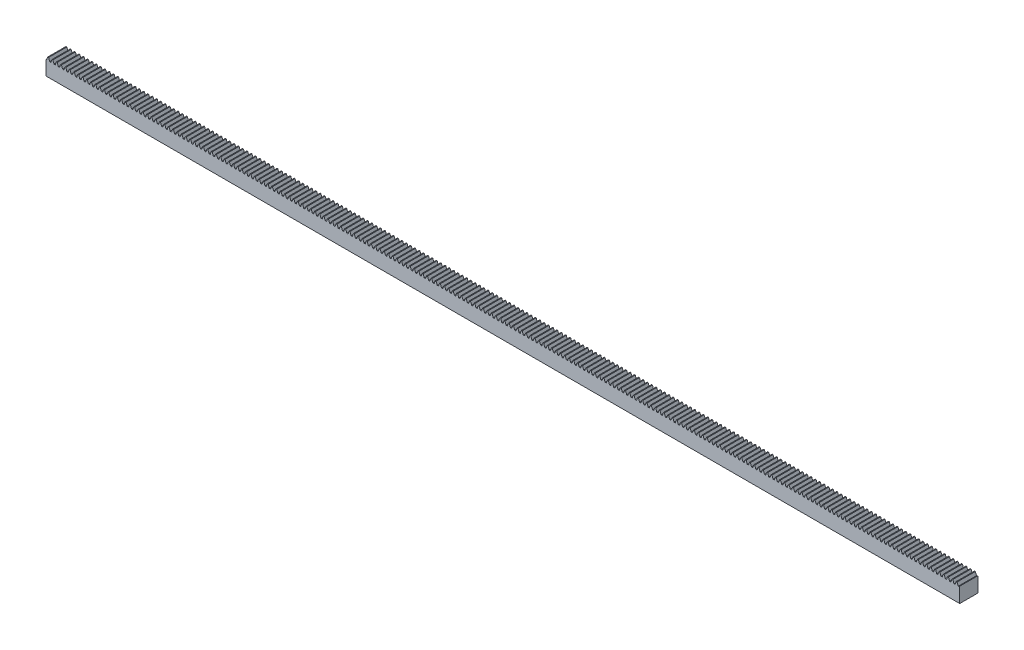
SolidWorks part; units mm, degrees
extrude "Blank" add sketch "BlankSke" against normal blind 8
sketch "BlankSke" plane through (0, 0, 0) normal (0, 0, 1) x (1, 0, 0)
  line L1 (0, 0) -> (400, 0)
  line L2 (0, 0) -> (0, 7.6)
  line L3 (0, 7.6) -> (400, 7.6)
  line L4 (400, 0) -> (400, 7.6)
  dimension "Length" = 400
ref_plane "Plane1" through (0, 0, 0) normal (0, 0, 1) x (1, 0, 0)
ref_plane "Plane2" through (0, 0, 0) normal (0, 1, 0) x (1, 0, 0)
ref_plane "Plane3" through (0, 0, 0) normal (1, 0, 0) x (0, 0, -1)
sketch "HoldingSke" plane through (0, 0, 0) normal (0, 1, 0) x (1, 0, 0)
  line L0 (0, 0) -> (0.232, 1.6504)
  line L1 (-15, 0) -> (100, 0) construction
  line L2 (0, 0) -> (-2.1039, 2.3779)
  line L3 (0, 0) -> (-11.863, 4.5341)
  line L4 (0, 0) -> (-7.1596, -4.8292)
  line L5 (0, 0) -> (-23.7986, -8.8762)
  line L6 (0, 0) -> (-10.5278, -7.1032)
  line L9 (-71.009, 38.7566) -> (304.8681, 175.5647)
  line L10 (-76.2, 2.9779) -> (-69.2, 2.9779)
  line L11 (0, 0) -> (-8, 0)
  line L12 (-76.2, 101.6) -> (-76.177, 101.6)
  line L13 (24.9733, 27.94) -> (52.9518, 28.4284)
  line L14 (24.9733, 27.94) -> (24.9743, 27.94)
  line L15 (24.9733, 27.94) -> (100.4006, 29.5858)
  circle A0 centre (0, 0) radius 19.05
  circle A1 centre (0, 0) radius 3.5
  circle A2 centre (0, 0) radius 12.7
  dimension "Num_teeth" = 214
  dimension "Width" = 8
  dimension "Length" = 400
  dimension "Pitch_height" = 7
sketch "TooCutSkeIll" plane through (0, 0, 0) normal (0, 0, 1) x (1, 0, 0)
  line L0 (-0.7529, 7.5842) -> (-0.3034, 6.3494)
  line L1 (-0.1615, 6.25) -> (0.1615, 6.25)
  line L2 (0.3034, 6.3494) -> (0.7529, 7.5842)
  line L3 (400, 7.6) -> (0, 7.6) construction
  line L4 (0, 0) -> (0, 64.897) construction
  line L5 (-13.208, 7) -> (12.954, 7) construction
  line L6 (0, 0) -> (400, 0) construction
  line L7 (0.5402, 7) -> (0.5402, 48.7463) construction
  line L8 (-0.5402, 7) -> (-0.5402, 48.7463) construction
  line L9 (0.7754, 7.6) -> (0.7754, 7.6254)
  line L10 (-0.7754, 7.6) -> (-0.7754, 7.6254)
  line L11 (-0.7754, 7.6254) -> (0.7754, 7.6254)
  arc A0 (0.1615, 6.25) -> (0.3034, 6.3494) centre (0.1615, 6.401) ccw
  arc A1 (-0.3034, 6.3494) -> (-0.1615, 6.25) centre (-0.1615, 6.401) ccw
  arc A2 (0.7754, 7.6) -> (0.7529, 7.5842) centre (0.7754, 7.576) ccw
  arc A3 (-0.7529, 7.5842) -> (-0.7754, 7.6) centre (-0.7754, 7.576) ccw
  dimension "Addendum_plus" = 0.6254
  dimension "Pitch_height" = 7
  dimension "Pressure_angle" = 20
  dimension "Gap_width" = 1.0805
  dimension "Dedendum" = 0.75
extrude "ToothCutIll" [suppressed] cut sketch "TooCutSkeIll" against normal through all
sketch "TooCutSkeSim" plane through (0, 0, 0) normal (0, 0, 1) x (1, 0, 0)
  line L0 (0.2673, 6.25) -> (-0.2673, 6.25)
  line L1 (0.7679, 7.6254) -> (0.2673, 6.25)
  line L2 (0, 17.4625) -> (0, 53.467) construction
  line L3 (0.7679, 7.6254) -> (-0.7679, 7.6254)
  line L6 (-0.7679, 7.6254) -> (-0.2673, 6.25)
  line L9 (-0.5402, 7) -> (0.5402, 7) construction
  line L10 (0, 0) -> (400, 0) construction
  line L11 (0.5402, 7) -> (0.5402, 53.467) construction
  line L12 (-0.5402, 7) -> (-0.5402, 53.467) construction
  dimension "Addendum_plus" = 0.6254
  dimension "Pitch_height" = 7
  dimension "Pressure_angle" = 20
  dimension "Gap_width" = 1.0805
  dimension "Dedendum" = 0.75
extrude "ToothCutSim" cut sketch "TooCutSkeSim" against normal through all
pattern_linear "TeethCuts" count 214 spacing 1.885 along (1, 0, 0) of "ToothCutIll", "ToothCutSim"
equation "' \"Module@HoldingSke\" = 6.35"
equation "' \"Num_teeth@HoldingSke\" = 12"
equation "' \"Ap@HoldingSke\" =  20"
equation "' \"Ap@HoldingSke\" = 20"
equation "' \"Width@HoldingSke\" = 0.25 * 25.4"
equation "' \"Show_teeth@HoldingSke\" = 500"
equation "' \"Backlash@HoldingSke\" = 0.009 * 25.4"
equation "' \"Addendum_fac@HoldingSke\" = 1.0"
equation "' \"Dedendum_fac@HoldingSke\" = 1.25"
equation "' \"Dedendum_add@HoldingSke\" = 0.00005 * 25.4"
equation "' \"Clearance_fac@HoldingSke\" = 0.25"
equation "' \"Pitch_height@HoldingSke\" = 1 * 25.4"
equation "' \"Length@HoldingSke\" = 4.71 * 25.4"
equation "\"Pitch@HoldingSke\" = 1 / \"Module@HoldingSke\""
equation "\"MPH@HoldingSke\" = \"Dedendum_fac@HoldingSke\" / \"Pitch@HoldingSke\" + 2 * \"Dedendum_add@HoldingSke\" + 0.002 * 25.4"
equation "\"MPH@HoldingSke\" = ((sgn( \"MPH@HoldingSke\" - \"Pitch_height@HoldingSke\")+1)*( \"MPH@HoldingSke\" - \"Pitch_height@HoldingSke\"))/2 + \"Pitch_height@HoldingSke\""
equation "\"Blank_height@BlankSke\" = \"Pitch_height@HoldingSke\" + \"Addendum_fac@HoldingSke\"  / \"Pitch@HoldingSke\" "
equation "\"Length@BlankSke\" =  \"Length@HoldingSke\""
equation "\"Face_width@Blank\" = \"Width@HoldingSke\""
equation "\"Pressure_angle@TooCutSkeIll\" = \"Ap@HoldingSke\""
equation "\"Addendum_plus@TooCutSkeIll\" =  \"Addendum_fac@HoldingSke\"  / \"Pitch@HoldingSke\" + 0.001 *25.4"
equation "\"Dedendum@TooCutSkeIll\" = \"Dedendum_fac@HoldingSke\"  / \"Pitch@HoldingSke\""
equation "\"Pitch_height@TooCutSkeIll\" =  \"MPH@HoldingSke\""
equation "\"Gap_width@TooCutSkeIll\" = 3.14159265 / 2 / \"Pitch@HoldingSke\" + 6 * \"Backlash@HoldingSke\""
equation "\"Pressure_angle@TooCutSkeSim\" = \"Ap@HoldingSke\""
equation "\"Addendum_plus@TooCutSkeSim\" =  \"Addendum_fac@HoldingSke\"  / \"Pitch@HoldingSke\" + 0.001 * 25.4"
equation "\"Dedendum@TooCutSkeSim\" = \"Dedendum_fac@HoldingSke\"  / \"Pitch@HoldingSke\""
equation "\"Pitch_height@TooCutSkeSim\" =  \"MPH@HoldingSke\""
equation "\"Gap_width@TooCutSkeSim\" = 3.14159265 / 2 / \"Pitch@HoldingSke\" + 6 * \"Backlash@HoldingSke\""
equation "\"Root_fillet@TooCutSkeIll\" = \"Clearance_fac@HoldingSke\" / \"Pitch@HoldingSke\" + \"Dedendum_add@HoldingSke\""
equation "\"Break_rad@TooCutSkeIll\" = 0.02 / \"Pitch@HoldingSke\" * 2"
equation "\"Linear_pitch@TeethCuts\" = 3.14159265 / \"Pitch@HoldingSke\""
equation "\"Num_teeth@HoldingSke\" = int( ( \"Length@HoldingSke\" + 0 ) / (3.14159265 / \"Pitch@HoldingSke\")) + 0.9999  + 1"
equation " \"Num_teeth@TeethCuts\" = int( \"Show_teeth@HoldingSke\" ) + 1"
equation " \"Num_teeth@TeethCuts\" = ((sgn( \"Num_teeth@TeethCuts\" - \"Num_teeth@HoldingSke\" )-1)*( \"Num_teeth@TeethCuts\" - \"Num_teeth@HoldingSke\" ))/-2+ \"Num_teeth@HoldingSke\""
equation " \"Num_teeth@TeethCuts\" = ((sgn( \"Num_teeth@TeethCuts\" - 2.0)+1)*( \"Num_teeth@TeethCuts\" - 2.0))/2 +2.0"
